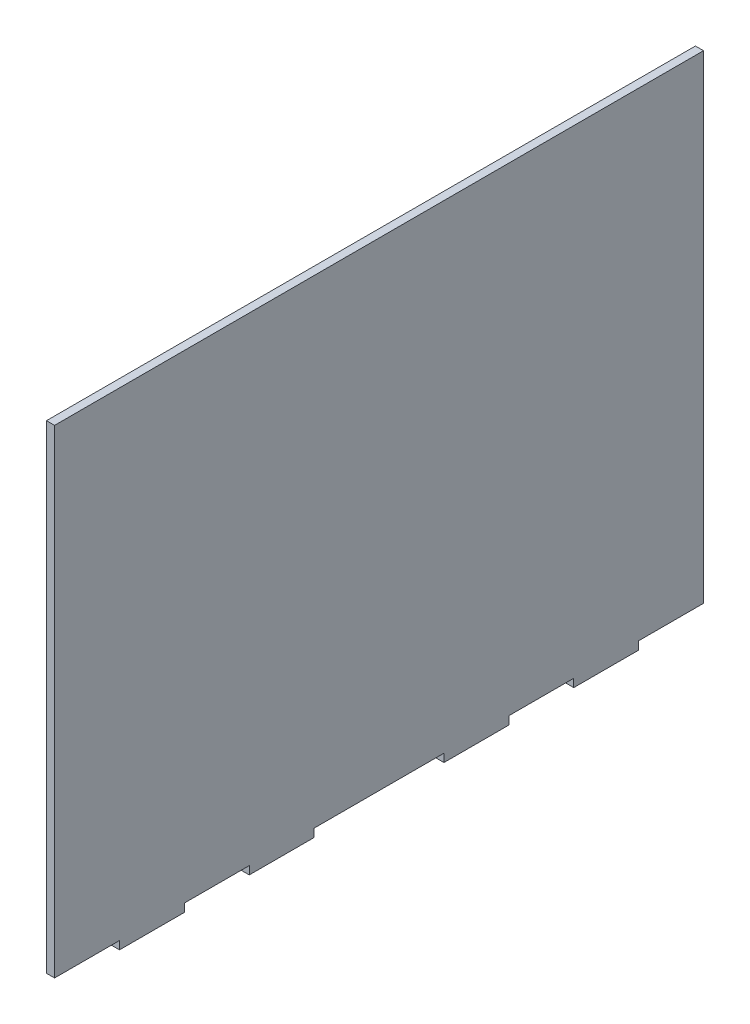
SolidWorks part; units mm, degrees
ref_plane "Front" through (0, 0, 0) normal (0, 0, 1) x (1, 0, 0)
ref_plane "Top" through (0, 0, 0) normal (0, 1, 0) x (1, 0, 0)
ref_plane "Right" through (0, 0, 0) normal (1, 0, 0) x (0, 0, -1)
sketch "Skizze1" plane through (0, 0, 0) normal (1, 0, 0) x (0, 0, -1)
  line L0 (200, 0) -> (-200, 0)
  line L1 (-200, 0) -> (-200, 300)
  line L2 (-200, 300) -> (200, 300)
  line L3 (0, 300) -> (0, 0) construction
  line L4 (200, 0) -> (200, 300)
  dimension "D1" = 400
  dimension "D2" = 300
extrude "Aufsatz-Linear austragen1" add sketch "Skizze1" along normal blind 5
sketch "Skizze2" plane through (5, 0, 0) normal (1, 0, 0) x (0, 0, -1)
  line L5 (-200, 0) -> (200, 0) construction
  line L11 (-200, 0) -> (-160, 0)
  line L12 (-200, 0) -> (-200, 5)
  line L13 (-200, 5) -> (-160, 5)
  line L14 (0, 0) -> (0, 300) construction
  line L15 (200, 300) -> (-200, 300) construction
  line L16 (-160, 0) -> (-160, 5)
  line L17 (-120, 0) -> (-80, 0)
  line L26 (-120, 0) -> (-120, 5)
  line L27 (-120, 5) -> (-80, 5)
  line L28 (-80, 0) -> (-80, 5)
  line L29 (-160, 5) -> (-120, 5) construction
  line L30 (-80, 5) -> (-40, 5) construction
  line L31 (40, 0) -> (-40, 0)
  line L32 (-40, 0) -> (-40, 5)
  line L34 (40, 0) -> (40, 5)
  line L35 (80, 5) -> (40, 5) construction
  line L36 (160, 5) -> (120, 5) construction
  line L37 (80, 0) -> (80, 5)
  line L38 (120, 5) -> (80, 5)
  line L39 (120, 0) -> (120, 5)
  line L40 (120, 0) -> (80, 0)
  line L41 (160, 0) -> (160, 5)
  line L42 (200, 5) -> (160, 5)
  line L43 (200, 0) -> (200, 5)
  line L44 (200, 0) -> (160, 0)
  line L45 (-40, 5) -> (0, 5) construction
  line L46 (-40, 5) -> (40, 5)
  point P14 (0, 7.2519)
  dimension "D1" = 40
  dimension "D2" = 5
extrude "Schnitt-Linear austragen1" cut sketch "Skizze2" against normal through all
